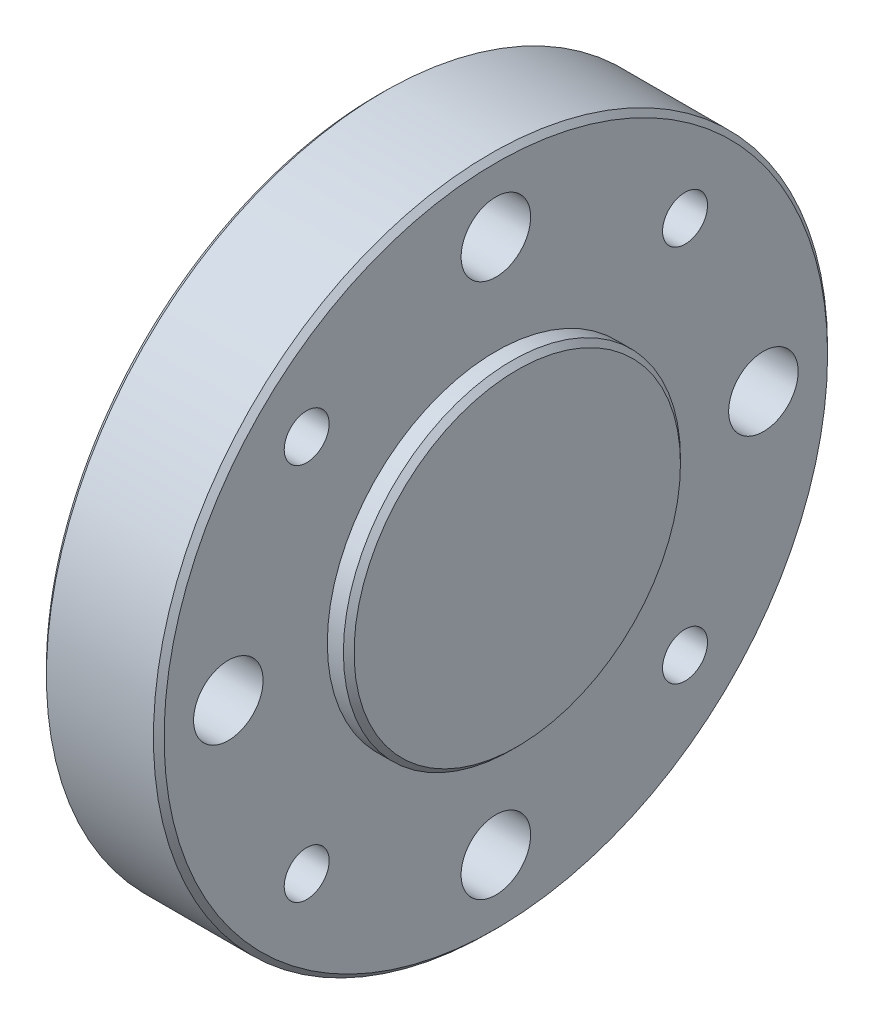
SolidWorks part; units mm, degrees
material "7079 Alloy"
ref_plane "Front Plane" through (0, 0, 0) normal (0, 0, 1) x (1, 0, 0)
ref_plane "Top Plane" through (0, 0, 0) normal (0, 1, 0) x (1, 0, 0)
ref_plane "Right Plane" through (0, 0, 0) normal (1, 0, 0) x (0, 0, -1)
sketch "Sketch1" plane through (0, 0, 0) normal (1, 0, 0) x (0, 0, -1)
  circle A0 centre (0, 0) radius 31.5
  dimension "D1" = 63
extrude "Boss-Extrude1" add sketch "Sketch1" along normal blind 11
sketch "Sketch2" plane through (0, 0, 0) normal (-1, 0, 0) x (0, 0, 1)
  circle A0 centre (0, 0) radius 25 construction
  circle A1 centre (0, 25) radius 3.25
  circle A2 centre (0, -25) radius 3.25
  dimension "D1" = 50
  dimension "D2" = 6.5
extrude "Cut-Extrude1" cut sketch "Sketch2" against normal through all
sketch "Sketch3" plane through (0, 0, 0) normal (-1, 0, 0) x (0, 0, 1)
  circle A0 centre (0, 25) radius 6
  circle A1 centre (0, -25) radius 6
  dimension "D1" = 12
extrude "Cut-Extrude2" cut sketch "Sketch3" against normal blind 5
chamfer "Chamfer1" distance 0.5 angle 45 2 edges at (0, 0, -31.5) (11, 0, -31.5)
sketch "Sketch4" plane through (11, 0, 0) normal (1, 0, 0) x (0, 0, -1)
  circle A0 centre (0, 0) radius 15.75
  dimension "D1" = 31.5
extrude "Boss-Extrude2" add sketch "Sketch4" along normal blind 2
chamfer "Chamfer2" distance 0.5 angle 45 1 edges at (13, 0, -15.75)
sketch "Sketch5" plane through (0, 0, 0) normal (-1, 0, 0) x (0, 0, 1)
  circle A0 centre (0, 0) radius 10.5
  circle A1 centre (0, 0) radius 18
  dimension "D1" = 21
  dimension "D2" = 36
extrude "Boss-Extrude3" [suppressed] add sketch "Sketch5" along normal blind 23
sketch "Sketch6" [suppressed] plane through (-23, 0, 0) normal (-1, 0, 0) x (0, 0, 1)
  line L1 (-8.5, 6.1644) -> (8.5, 6.1644)
  line L2 (-8.5, 6.1644) -> (-8.5, -6.1644)
  line L3 (-8.5, -6.1644) -> (8.5, -6.1644)
  line L4 (8.5, 6.1644) -> (8.5, -6.1644)
  circle A0 centre (0, 0) radius 10.5 construction
  circle A1 centre (0, 0) radius 10.5
  circle M7 centre (0, 0) radius 10.5
  dimension "D1" = 8.5
  dimension "D2" = 12.3288
extrude "Boss-Extrude4" [suppressed] add sketch "Sketch6" against normal up to next contours L4 M7 | L2 M7
sketch "Sketch7" [suppressed] plane through (-23, 0, 0) normal (-1, 0, 0) x (0, 0, 1)
  line L0 (8.5, 6.1644) -> (8.5, -6.1644) construction
  line L1 (-14.5, 10.6654) -> (14.5, 10.6654)
  line L2 (-14.5, 10.6654) -> (-14.5, -10.6654)
  line L3 (-14.5, -10.6654) -> (14.5, -10.6654)
  line L4 (14.5, 10.6654) -> (14.5, -10.6654)
  circle A1 centre (0, 0) radius 18
  circle A2 centre (0, 0) radius 18
  circle M6 centre (0, 0) radius 18
  dimension "D2" = 6
  dimension "D1" = 0
extrude "Cut-Extrude3" [suppressed] cut sketch "Sketch7" against normal blind 22 contours L4 M6 | L2 M6
sketch "Sketch8" [suppressed] plane through (0, 0, 14.5) normal (0, 0, 1) x (1, 0, 0)
  line L0 (-23, 10.6654) -> (-23, -10.6654) construction
  line L1 (-18, 4) -> (-6, 4) construction
  line L2 (-18, 4) -> (-18, -4)
  line L3 (-18, -4) -> (-6, -4) construction
  line L4 (-6, 4) -> (-6, -4)
  line L5 (-6, 0) -> (0, 0) construction
  circle A0 centre (-18, 4) radius 1.75
  circle A1 centre (-6, 4) radius 1.75
  circle A2 centre (-6, -4) radius 1.75
  circle A3 centre (-18, -4) radius 1.75
  dimension "D4" = 3.5
  dimension "D1" = 5
  dimension "D2" = 12
  dimension "D3" = 8
extrude "Cut-Extrude4" [suppressed] cut sketch "Sketch8" against normal through all contours A0 | A1 | A2 | A3
pattern_circular "CirPattern1" count 4 over 360 about axis through (11, 0, 0) along (-1, 0, 0) of "Cut-Extrude2", "Cut-Extrude1" reverse direction yes
sketch "Sketch9" [suppressed] plane through (-23, 0, 0) normal (-1, 0, 0) x (0, 0, 1)
  line L0 (-8.5, 6.1644) -> (-8.5, -6.1644) construction
  line L1 (8.5, 6.1644) -> (8.5, -6.1644) construction
  line L2 (-8.5, 6.1644) -> (-8.5, -6.1644)
  line L3 (8.5, 6.1644) -> (8.5, -6.1644)
  line L4 (-8.6, 6.1968) -> (-8.6, -6.1968)
  line L5 (8.6, 6.1968) -> (8.6, -6.1968)
  arc A0 (-8.5, -6.1644) -> (8.5, -6.1644) centre (0, 0) ccw construction
  arc A1 (8.5, 6.1644) -> (-8.5, 6.1644) centre (0, 0) ccw construction
  arc A2 (-8.5, -6.1644) -> (8.5, -6.1644) centre (0, 0) ccw
  arc A3 (8.5, 6.1644) -> (-8.5, 6.1644) centre (0, 0) ccw
  arc A4 (8.6, 6.1968) -> (-8.6, 6.1968) centre (0, 0) ccw
  arc A5 (-8.6, -6.1968) -> (8.6, -6.1968) centre (0, 0) ccw
  dimension "D1" = 0.1
sketch "Sketch10" plane through (0, 0, 0) normal (-1, 0, 0) x (0, 0, 1)
  line L0 (-17.6777, 17.6777) -> (17.6777, -17.6777) construction
  line L1 (-17.6777, -17.6777) -> (17.6777, -17.6777)
  line L2 (-17.6777, -17.6777) -> (-17.6777, 17.6777)
  line L3 (-17.6777, 17.6777) -> (17.6777, 17.6777)
  line L4 (17.6777, -17.6777) -> (17.6777, 17.6777)
  dimension "D1" = 25
  dimension "D2" = 50
hole_wizard "M5 Tapped Hole1" positions "3DSketch1" profile "Sketch11" tap size "M5" standard "ISO" end condition through all
sketch3d "3DSketch1"
  point P0 (0, 17.6777, -17.6777)
  point P3 (0, 17.6777, 17.6777)
  point P6 (0, -17.6777, -17.6777)
  point P9 (0, -17.6777, 17.6777)
sketch "Sketch11" plane through (0, 17.6777, -17.6777) normal (0, 1, 0) x (0, 0, 1)
  line L0 (0, 0) -> (0, 13)
  line L1 (0, 13) -> (2.1, 13)
  line L2 (2.1, 13) -> (2.1, 0)
  line L5 (2.1, 0) -> (0, 0)
  line L11 (0, -6.35) -> (0, 107.95) construction
  dimension "Thru Tap Drill Dia." = 4.2
  dimension "Thru Tap Drill Depth" = 13
cosmetic thread "Hole Thread1" parameters "D2"=5
cosmetic thread "Hole Thread2" parameters "D2"=5
cosmetic thread "Hole Thread3" parameters "D2"=5
cosmetic thread "Hole Thread4" parameters "D2"=5
